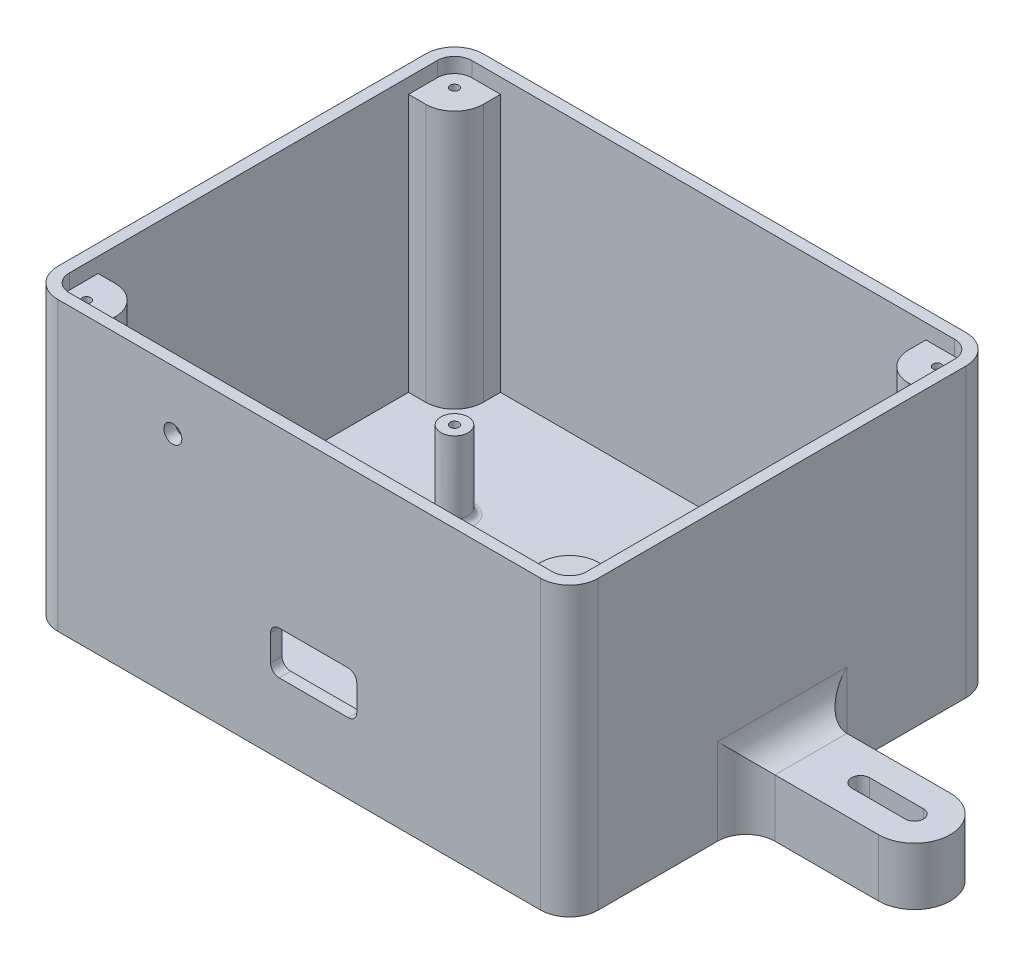
SolidWorks part; units mm, degrees
ref_plane "Plano frontal" through (0, 0, 0) normal (0, 0, 1) x (1, 0, 0)
ref_plane "Plano superior" through (0, 0, 0) normal (0, 1, 0) x (1, 0, 0)
ref_plane "Plano direito" through (0, 0, 0) normal (1, 0, 0) x (0, 0, -1)
ref_plane "Plano1" through (0, 0, -4.75) normal (0, 0, 1) x (1, 0, 0)
sketch "Esboço1" plane through (0, 0, -4.75) normal (0, 0, 1) x (1, 0, 0)
  line L0 (100, 27) -> (95.25, 27)
  line L1 (95.25, 27) -> (95.25, 26)
  line L2 (95.25, 26) -> (100, 26)
  line L3 (100, 26) -> (100, 27)
  line L4 (95.25, 27) -> (95.25, 26) construction
revolve "Revolução1" add sketch "Esboço1" angle 180 about L4 reverse direction yes
sketch "Esboço2" plane through (0, 0, -4.75) normal (0, 0, 1) x (1, 0, 0)
  line L0 (90.5, 100) -> (100, 100)
  line L1 (100, 100) -> (100, 26)
  line L2 (100, 26) -> (90.5, 26)
  line L3 (90.5, 26) -> (90.5, 100)
extrude "Ressalto-extrusão1" add sketch "Esboço2" along normal blind 8.75
sketch "Esboço3" plane through (90.5, 0, 0) normal (-1, 0, 0) x (0, 0, 1)
  line L0 (-4.75, 27) -> (4, 27)
  line L1 (4, 27) -> (4, 100)
  line L2 (4, 100) -> (-4.75, 100)
  line L3 (-4.75, 100) -> (-4.75, 27)
extrude "Corte-extrusão1" cut sketch "Esboço3" against normal blind 1.5
sketch "Esboço4" plane through (0, 0, -4.75) normal (0, 0, -1) x (-1, 0, 0)
  line L0 (-92, 27) -> (-92, 100)
  line L1 (-92, 100) -> (-100, 100)
  line L2 (-100, 100) -> (-100, 27)
  line L3 (-100, 27) -> (-92, 27)
extrude "Corte-extrusão2" cut sketch "Esboço4" against normal blind 4.75
sketch "Esboço5" plane through (92, 0, 0) normal (-1, 0, 0) x (0, 0, 1)
  line L0 (4, 32) -> (0, 32)
  line L1 (0, 32) -> (0, 100)
  line L2 (0, 100) -> (4, 100)
  line L3 (4, 100) -> (4, 32)
extrude "Ressalto-extrusão2" add sketch "Esboço5" along normal blind 52
sketch "Esboço6" plane through (40, 0, 0) normal (-1, 0, 0) x (0, 0, 1)
  line L0 (4, 26) -> (0, 26)
  line L1 (0, 26) -> (0, 100)
  line L2 (0, 100) -> (4, 100)
  line L3 (4, 100) -> (4, 26)
extrude "Ressalto-extrusão3" add sketch "Esboço6" along normal blind 80
sketch "Esboço7" plane through (100, 0, 0) normal (1, 0, 0) x (0, 0, -1)
  line L0 (0, 100) -> (0, 26)
  line L1 (0, 26) -> (-4, 26)
  line L2 (-4, 26) -> (-4, 100)
  line L3 (-4, 100) -> (0, 100)
extrude "Ressalto-extrusão4" add sketch "Esboço7" along normal blind 40
sketch "Esboço8" plane through (140, 0, 0) normal (1, 0, 0) x (0, 0, -1)
  line L0 (140, 26) -> (-4, 26)
  line L1 (-4, 26) -> (-4, 100)
  line L2 (-4, 100) -> (140, 100)
  line L3 (140, 100) -> (140, 26)
extrude "Ressalto-extrusão5" add sketch "Esboço8" along normal blind 4
sketch "Esboço9" plane through (-40, 0, 0) normal (-1, 0, 0) x (0, 0, 1)
  line L0 (-140, 26) -> (-140, 100)
  line L1 (-140, 100) -> (4, 100)
  line L2 (4, 100) -> (4, 26)
  line L3 (4, 26) -> (-140, 26)
extrude "Ressalto-extrusão6" add sketch "Esboço9" along normal blind 4
sketch "Esboço10" plane through (0, 0, -140) normal (0, 0, -1) x (-1, 0, 0)
  line L0 (-144, 26) -> (-144, 100)
  line L1 (-144, 100) -> (44, 100)
  line L2 (44, 100) -> (44, 26)
  line L3 (44, 26) -> (-144, 26)
extrude "Ressalto-extrusão7" add sketch "Esboço10" along normal blind 4
sketch "Esboço11" plane through (0, 26, 0) normal (0, -1, 0) x (1, 0, 0)
  line L0 (144, -144) -> (-44, -144)
  line L1 (-44, -144) -> (-44, 4)
  line L2 (-44, 4) -> (144, 4)
  line L3 (144, 4) -> (144, -144)
extrude "Ressalto-extrusão8" add sketch "Esboço11" along normal blind 26
sketch "Esboço12" plane through (0, 26, 0) normal (0, 1, 0) x (-1, 0, 0)
  line L0 (-140, -140) -> (40, -140)
  line L1 (40, -140) -> (40, 0)
  line L2 (40, 0) -> (-90.5, 0)
  line L3 (-90.5, 0) -> (-90.5, -4.75)
  line L4 (-100, -4.75) -> (-100, 0)
  line L5 (-100, 0) -> (-140, 0)
  line L6 (-140, 0) -> (-140, -140)
  arc A0 (-90.5, -4.75) -> (-100, -4.75) centre (-95.25, -4.75) cw
extrude "Corte-extrusão3" cut sketch "Esboço12" against normal blind 21
ref_plane "Plano2" through (0, 0, 0) normal (0, -1, 0) x (1, 0, 0)
sketch "Esboço13" plane through (0, 0, 0) normal (0, -1, 0) x (1, 0, 0)
  line L0 (144, -82.5) -> (190, -82.5)
  line L1 (190, -57.5) -> (144, -57.5)
  line L2 (144, -57.5) -> (144, -82.5)
  arc A0 (190, -82.5) -> (190, -57.5) centre (190, -70) ccw
extrude "Ressalto-extrusão9" add sketch "Esboço13" against normal blind 20
sketch "Esboço14" plane through (0, 0, 0) normal (0, -1, 0) x (1, 0, 0)
  line L0 (190, -66.875) -> (171.25, -66.875)
  line L1 (171.25, -73.125) -> (190, -73.125)
  arc A0 (190, -73.125) -> (190, -66.875) centre (190, -70) ccw
  arc A1 (171.25, -66.875) -> (171.25, -73.125) centre (171.25, -70) ccw
extrude "Corte-extrusão4" cut sketch "Esboço14" against normal through all
sketch "Esboço15" plane through (0, 0, 0) normal (0, -1, 0) x (1, 0, 0)
  line L0 (-44, -57.5) -> (-90, -57.5)
  line L1 (-90, -82.5) -> (-44, -82.5)
  line L2 (-44, -82.5) -> (-44, -57.5)
  arc A0 (-90, -57.5) -> (-90, -82.5) centre (-90, -70) ccw
extrude "Ressalto-extrusão10" add sketch "Esboço15" against normal blind 20
sketch "Esboço16" plane through (0, 20, 0) normal (0, 1, 0) x (-1, 0, 0)
  line L0 (71.25, -73.125) -> (90, -73.125)
  line L1 (90, -66.875) -> (71.25, -66.875)
  arc A0 (71.25, -66.875) -> (71.25, -73.125) centre (71.25, -70) ccw
  arc A1 (90, -73.125) -> (90, -66.875) centre (90, -70) ccw
extrude "Corte-extrusão5" cut sketch "Esboço16" against normal through all
sketch "Esboço17" plane through (0, 5, 0) normal (0, 1, 0) x (-1, 0, 0)
  line L0 (24, -124) -> (40, -124)
  line L1 (40, -124) -> (40, -140)
  line L2 (40, -140) -> (24, -140)
  line L3 (24, -140) -> (24, -124)
extrude "Ressalto-extrusão11" add sketch "Esboço17" along normal blind 90
sketch "Esboço18" plane through (0, 5, 0) normal (0, 1, 0) x (-1, 0, 0)
  line L0 (-124, -140) -> (-140, -140)
  line L1 (-140, -140) -> (-140, -124)
  line L2 (-140, -124) -> (-124, -124)
  line L3 (-124, -124) -> (-124, -140)
extrude "Ressalto-extrusão12" add sketch "Esboço18" along normal blind 90
sketch "Esboço19" plane through (0, 5, 0) normal (0, 1, 0) x (-1, 0, 0)
  line L0 (-124, -16) -> (-140, -16)
  line L1 (-140, -16) -> (-140, 0)
  line L2 (-140, 0) -> (-124, 0)
  line L3 (-124, 0) -> (-124, -16)
extrude "Ressalto-extrusão13" add sketch "Esboço19" along normal blind 90
sketch "Esboço20" plane through (0, 5, 0) normal (0, 1, 0) x (-1, 0, 0)
  line L0 (24, -16) -> (24, 0)
  line L1 (24, 0) -> (40, 0)
  line L2 (40, 0) -> (40, -16)
  line L3 (40, -16) -> (24, -16)
extrude "Ressalto-extrusão14" add sketch "Esboço20" along normal blind 90
sketch "Esboço21" plane through (0, 5, 0) normal (0, 1, 0) x (-1, 0, 0)
  line L0 (-9.5, -4.75) -> (-9.5, 0)
  line L1 (-9.5, 0) -> (0, 0)
  line L2 (0, 0) -> (0, -4.75)
  arc A0 (0, -4.75) -> (-9.5, -4.75) centre (-4.75, -4.75) cw
extrude "Ressalto-extrusão15" add sketch "Esboço21" along normal blind 22
ref_plane "Plano3" through (0, 0, -95.25) normal (0, 0, 1) x (1, 0, 0)
sketch "Esboço22" plane through (0, 0, -95.25) normal (0, 0, 1) x (1, 0, 0)
  line L0 (9.5, 27) -> (4.75, 27)
  line L1 (4.75, 27) -> (4.75, 5)
  line L2 (4.75, 5) -> (9.5, 5)
  line L3 (9.5, 5) -> (9.5, 27)
  line L4 (4.75, 27) -> (4.75, 5) construction
revolve "Revolução2" add sketch "Esboço22" angle 360 about L4 reverse direction yes
hole_wizard "Furo de diâmetro Ø3.0 (3)1" positions "Esboço24" profile "Esboço23" hole size "Ø3.0" standard "Ansi Metric"
sketch "Esboço24" plane through (0, 95, 0) normal (0, 1, 0) x (1, 0, 0)
  point P0 (-34, 6)
  point P1 (134, 6)
  point P2 (134, 134)
  point P3 (-34, 134)
sketch "Esboço23" plane through (-34, 95, -6) normal (1, 0, 0) x (0, 0, 1)
  line L0 (0, 0) -> (0, 15.9013)
  line L1 (0, 15.9013) -> (1.5, 15)
  line L2 (1.5, 15) -> (1.5, 0)
  line L5 (1.5, 0) -> (0, 0)
  line L10 (0, 15.9013) -> (-1.5, 15) construction
  line L11 (0, -6.35) -> (0, 107.95) construction
  dimension "Hole Dia." = 3
  dimension "Hole Depth" = 15
  dimension "Drill Angle" = 118
hole_wizard "Furo de diâmetro Ø3.0 (3)2" positions "Esboço26" profile "Esboço25" hole size "Ø3.0" standard "Ansi Metric"
sketch "Esboço26" plane through (0, 27, 0) normal (0, 1, 0) x (1, 0, 0)
  point P0 (95.25, 4.75)
  point P1 (4.75, 4.75)
  point P2 (4.75, 95.25)
sketch "Esboço25" plane through (95.25, 27, -4.75) normal (1, 0, 0) x (0, 0, 1)
  line L0 (0, 0) -> (0, 15.9013)
  line L1 (0, 15.9013) -> (1.5, 15)
  line L2 (1.5, 15) -> (1.5, 0)
  line L5 (1.5, 0) -> (0, 0)
  line L10 (0, 15.9013) -> (-1.5, 15) construction
  line L11 (0, -6.35) -> (0, 107.95) construction
  dimension "Hole Dia." = 3
  dimension "Hole Depth" = 15
  dimension "Drill Angle" = 118
hole_wizard "Broca de rosquear para helicoide M61" positions "Esboço28" profile "Esboço27" hole size "M6x1.0" standard "Ansi Metric"
sketch "Esboço28" plane through (0, 0, 4) normal (0, 0, 1) x (1, 0, 0)
  point P0 (6, 79.5)
sketch "Esboço27" plane through (6, 79.5, 4) normal (1, 0, 0) x (0, -1, 0)
  line L0 (0, 0) -> (0, 4)
  line L1 (0, 4) -> (3.125, 4)
  line L2 (3.125, 4) -> (3.125, 0)
  line L5 (3.125, 0) -> (0, 0)
  line L11 (0, -6.35) -> (0, 107.95) construction
  dimension "Thru Hole Dia." = 6.25
  dimension "Thru Hole Depth" = 4
chamfer "Chanfro1" distance 0.025 angle 45 7 edges at (95.25, 27, -3.25) (4.75, 27, -93.75) (134, 95, -4.5) (-34, 95, -4.5) (4.75, 27, -3.25) (134, 95, -132.5) (-34, 95, -132.5)
fillet "Filete1" radius 2 3 edges at (92, 32, 2) (40, 26, 2) (40, 32, 2) tangent propagation no
fillet "Filete2" radius 10 18 edges at (124, 50, -124) (-44, 10, -82.5) (-44, 20, -70) (-44, 10, -57.5) (144, 10, -82.5) (144, 10, -57.5) (144, 20, -70) (140, 97.5, -140) (140, 97.5, 0) (-24, 50, -16) (-40, 97.5, 0) (-40, 97.5, -140) (144, 50, -144) (-24, 50, -124) (-44, 50, -144) (124, 50, -16) (-44, 50, 4) (144, 50, 4) tangent propagation no
sketch "Esboço35" plane through (0, 0, -95.25) normal (0, 0, 1) x (1, 0, 0)
  line L0 (100, 27) -> (95.25, 27)
  line L1 (95.25, 27) -> (95.25, 5)
  line L2 (95.25, 5) -> (100, 5)
  line L3 (100, 5) -> (100, 27)
  line L4 (95.25, 27) -> (95.25, 5) construction
revolve "Revolução3" add sketch "Esboço35" angle 360 about L1 reverse direction yes
sketch "Esboço42" plane through (0, 0, -95.25) normal (0, 0, 1) x (1, 0, 0)
  line L0 (96.775, 27) -> (95.25, 27)
  line L1 (95.25, 27) -> (95.25, 11.0987)
  line L2 (95.25, 11.0987) -> (96.75, 12)
  line L3 (96.75, 12) -> (96.75, 26.975)
  line L4 (96.75, 26.975) -> (96.775, 27)
  line L5 (95.25, 27) -> (95.25, 11.0987) construction
revolve "Corte-Revolução1" cut sketch "Esboço42" angle 360 about L1 reverse direction yes
fillet "Filete3" radius 2 8 edges at (0, 5, -2.375) (9.5, 5, -2.375) (4.75, 5, -9.5) (100, 5, -2.375) (95.25, 5, -9.5) (90.5, 5, -2.375) (95.25, 5, -100) (4.75, 5, -100)
sketch "Esboço43" plane through (0, 0, 4) normal (0, 0, 1) x (1, 0, 0)
  line L0 (42, 32) -> (40, 32) construction
  line L1 (90, 32) -> (92, 32) construction
  line L2 (42, 26) -> (40, 26) construction
  line L4 (40, 26) -> (92, 26)
  line L5 (40, 26) -> (40, 32)
  line L6 (40, 32) -> (92, 32)
  line L7 (92, 26) -> (92, 32)
extrude "Ressalto-extrusão16" add sketch "Esboço43" against normal blind 4
sketch "Esboço44" plane through (0, 27, 0) normal (0, 1, 0) x (-1, 0, 0)
  line L0 (-9.5, -4.75) -> (-9.5, 0)
  line L1 (-9.5, 0) -> (0, 0)
  line L2 (0, 0) -> (0, -4.75)
  line L3 (-100, 0) -> (-100, -4.75)
  line L4 (-90.5, 0) -> (-100, 0)
  line L5 (-90.5, -4.75) -> (-90.5, 0)
  circle A0 centre (-4.75, -95.25) radius 4.75
  circle A1 centre (-95.25, -95.25) radius 4.75
  arc A2 (-9.5, -4.75) -> (0, -4.75) centre (-4.75, -4.75) ccw
  circle A3 centre (-4.75, -95.25) radius 1.525
  circle A4 centre (-95.25, -95.25) radius 1.525
  circle A5 centre (-4.75, -4.75) radius 1.525
  circle A6 centre (-95.25, -4.75) radius 1.525
  arc A7 (-90.5, -4.75) -> (-100, -4.75) centre (-95.25, -4.75) cw
extrude "Ressalto-extrusão17" add sketch "Esboço44" along normal mid plane 10
sketch "Esboço47" plane through (0, 0, 4) normal (0, 0, 1) x (1, 0, 0)
  line L0 (100, 32) -> (40, 32) construction
  line L1 (0, 32) -> (100, 32) construction
  line L3 (43, 39.5) -> (67, 39.5)
  line L4 (40, 36.5) -> (40, 27.5)
  line L5 (43, 24.5) -> (67, 24.5)
  line L6 (70, 36.5) -> (70, 27.5)
  arc A0 (67, 39.5) -> (70, 36.5) centre (67, 36.5) cw
  arc A1 (67, 24.5) -> (70, 27.5) centre (67, 27.5) ccw
  arc A2 (40, 27.5) -> (43, 24.5) centre (43, 27.5) ccw
  arc A3 (43, 39.5) -> (40, 36.5) centre (43, 36.5) ccw
  point P9 (40, 32)
  point P12 (70, 39.5)
  point P15 (70, 24.5)
  point P20 (40, 39.5)
  dimension "D4" = 3
  dimension "D1" = 60
  dimension "D2" = 30
  dimension "D3" = 15
extrude "Corte-extrusão7" cut sketch "Esboço47" against normal blind 10
sketch "Esboço48" plane through (0, 100, 0) normal (0, 1, 0) x (1, 0, 0)
  line L2 (50, 0) -> (50, 24.1245) construction
  line L3 (11.5, 0) -> (88.5, 0) construction
  line L4 (140, 70) -> (123.7676, 70) construction
  line L5 (140, 16) -> (140, 124) construction
  line L6 (-34, 140) -> (-2.7651, 140)
  line L7 (-30, 140) -> (130, 140) construction
  line L8 (-40, 134) -> (-40, 108.9083)
  line L9 (-40, 124) -> (-40, 16) construction
  line L10 (-2.7651, 140) -> (-2.7651, 108.9083)
  line L11 (-2.7651, 108.9083) -> (-40, 108.9083)
  line L12 (140, 134) -> (140, 108.9083)
  line L13 (102.7651, 108.9083) -> (140, 108.9083)
  line L14 (102.7651, 140) -> (102.7651, 108.9083)
  line L15 (134, 140) -> (102.7651, 140)
  line L16 (-40, 6) -> (-40, 31.0917)
  line L17 (-2.7651, 31.0917) -> (-40, 31.0917)
  line L18 (-2.7651, 0) -> (-2.7651, 31.0917)
  line L19 (-34, 0) -> (-2.7651, 0)
  line L20 (134, 0) -> (102.7651, 0)
  line L21 (102.7651, 0) -> (102.7651, 31.0917)
  line L22 (102.7651, 31.0917) -> (140, 31.0917)
  line L23 (140, 6) -> (140, 31.0917)
  arc A0 (-34, 140) -> (-40, 134) centre (-34, 134) ccw
  arc A1 (134, 140) -> (140, 134) centre (134, 134) cw
  arc A2 (-34, 0) -> (-40, 6) centre (-34, 6) cw
  arc A3 (134, 0) -> (140, 6) centre (134, 6) ccw
  point P0 (-2.7651, 108.9083)
  point P14 (-30, 140)
  point P16 (-40, 140)
  point P21 (-39.2703, 140.7248)
  dimension "D1" = 6
extrude "Corte-extrusão8" cut sketch "Esboço48" against normal blind 5.2
